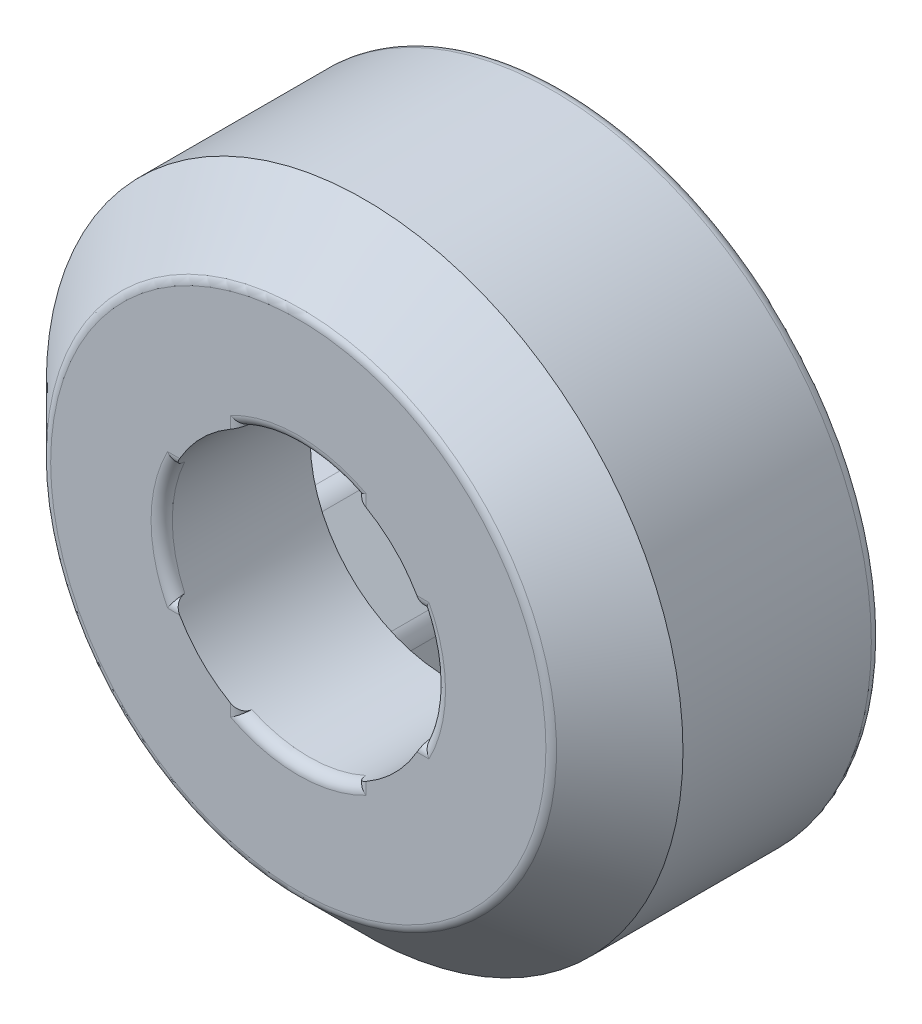
SolidWorks part; units mm, degrees
ref_plane "Front Plane" through (0, 0, 0) normal (0, 0, 1) x (1, 0, 0)
ref_plane "Top Plane" through (0, 0, 0) normal (0, 1, 0) x (1, 0, 0)
ref_plane "Right Plane" through (0, 0, 0) normal (1, 0, 0) x (0, 0, -1)
sketch "Sketch2" plane through (0, 0, 0) normal (0, 0, 1) x (1, 0, 0)
  line L0 (1.0775, 1.0775) -> (2.3387, 1.0775)
  line L1 (-2.3387, 1.0775) -> (-1.0775, 1.0775)
  line L2 (-1.0775, -1.0775) -> (-1.0775, -2.3387)
  line L3 (-2.3387, -1.0775) -> (-1.0775, -1.0775)
  line L4 (1.0775, -1.0775) -> (2.3387, -1.0775)
  line L5 (1.0775, -1.0775) -> (1.0775, -2.3387)
  line L6 (0, -2.575) -> (0, 2.575) construction
  line L8 (-1.0775, 2.3387) -> (-1.0775, 1.0775)
  line L10 (1.0775, 2.3387) -> (1.0775, 1.0775)
  circle A0 centre (0, 0) radius 4.95 construction
  arc A1 (-1.0775, -2.3387) -> (1.0775, -2.3387) centre (0, 0) ccw
  arc A2 (2.3387, -1.0775) -> (2.3387, 1.0775) centre (0, 0) ccw
  arc A3 (1.0775, 2.3387) -> (-1.0775, 2.3387) centre (0, 0) ccw
  arc A4 (-2.3387, 1.0775) -> (-2.3387, -1.0775) centre (0, 0) ccw
  point P7 (0, 0)
  point P12 (0, 0)
  dimension "D1" = 5.15
  dimension "D2" = 9.9
  dimension "D3" = 2.155
sketch "Sketch3" plane through (0, 0, 0) normal (1, 0, 0) x (0, 0, -1)
  line L0 (-1.5, 0) -> (3.5, 0)
  line L1 (-1.5, 0) -> (-1.5, 3.75)
  line L2 (3.5, 6) -> (5.2896, 6) construction
  line L3 (1.5, 0) -> (1.5, 1.7082) construction
  line L4 (1, 0) -> (1, 6) construction
  line L5 (3.5, 0) -> (3.5, 6)
  line L6 (-1.5, 3.75) -> (-4.0782, 3.75) construction
  line L7 (3.5, 6) -> (1, 6)
  line L8 (1, 6) -> (-1.5, 6)
  line L9 (-1.5, 6) -> (-1.5, 3.75)
  dimension "D1" = 1.5
  dimension "D2" = 3.75
  dimension "D3" = 3
  dimension "D4" = 2
  dimension "D5" = 6
  dimension "D6" = 2.5
revolve "Revolve1" add sketch "Sketch3" angle 360 about L0
extrude "Cut-Extrude1" cut sketch "Sketch2" against normal through all both and the other way through all
sketch "Sketch4" plane through (0, 0, -3.5) normal (0, 0, -1) x (-1, 0, 0)
  line L0 (0, 5) -> (0, 0) construction
  line L1 (0, 0) -> (-5, 0) construction
  line L2 (-1.5, 4.7697) -> (-1.5, 3.0962)
  line L3 (-1.5, 3.0962) -> (-3.0962, 1.5)
  line L4 (-3.0962, 1.5) -> (-4.7697, 1.5)
  line L5 (-1.5, 4.7697) -> (0, 4.7697) construction
  line L6 (-4.7697, 0) -> (-4.7697, 1.5) construction
  line L7 (1.5, 3.0962) -> (1.5, 4.7697)
  line L8 (3.0962, 1.5) -> (1.5, 3.0962)
  line L9 (4.7697, 1.5) -> (3.0962, 1.5)
  line L10 (3.0962, -1.5) -> (4.7697, -1.5)
  line L11 (1.5, -3.0962) -> (3.0962, -1.5)
  line L12 (1.5, -4.7697) -> (1.5, -3.0962)
  line L13 (-1.5, -3.0962) -> (-1.5, -4.7697)
  line L14 (-3.0962, -1.5) -> (-1.5, -3.0962)
  line L15 (-4.7697, -1.5) -> (-3.0962, -1.5)
  arc A0 (0, 5) -> (-1.5, 4.7697) centre (0, 0) ccw
  arc A1 (-4.7697, 1.5) -> (-5, 0) centre (0, 0) ccw
  arc A2 (1.5, 4.7697) -> (0, 5) centre (0, 0) ccw
  arc A3 (5, 0) -> (4.7697, 1.5) centre (0, 0) ccw
  arc A4 (4.7697, -1.5) -> (5, 0) centre (0, 0) ccw
  arc A5 (0, -5) -> (1.5, -4.7697) centre (0, 0) ccw
  arc A6 (-1.5, -4.7697) -> (0, -5) centre (0, 0) ccw
  arc A7 (-5, 0) -> (-4.7697, -1.5) centre (0, 0) ccw
  point P31 (0, 0)
  dimension "D1" = 5
  dimension "D2" = 3.25
  dimension "D3" = 1.5
  dimension "D4" = 45
  dimension "D5" = 4
extrude "Cut-Extrude2" cut sketch "Sketch4" against normal blind 2.2
fillet "Fillet1" radius 0.5 8 edges at (3.0962, -1.5, -2.4) (1.5, -3.0962, -2.4) (-1.5, -3.0962, -2.4) (-3.0962, -1.5, -2.4) (-3.0962, 1.5, -2.4) (-1.5, 3.0962, -2.4) (1.5, 3.0962, -2.4) (3.0962, 1.5, -2.4)
chamfer "Chamfer1" distance 1.25 angle 45 1 edges at (6, 0, 1.5)
fillet "Fillet2" radius 0.2 38 edges at (-1.0775, -1.7081, 1.5) (0, -2.575, 1.5) (1.0775, -1.7081, 1.5) (1.7081, -1.0775, 1.5) (2.575, 0, 1.5) (1.7081, 1.0775, 1.5) (1.0775, 1.7081, 1.5) (0, 2.575, 1.5) (-1.0775, 1.7081, 1.5) (-1.7081, 1.0775, 1.5) (-2.575, 0, 1.5) (-1.7081, -1.0775, 1.5) (6, 0, -3.5) (1.5381, -3.112, -3.5) (1.5, -4.0365, -3.5) (0, -5, -3.5) (-1.5, -4.0365, -3.5) (-1.5381, -3.112, -3.5) (-2.2981, -2.2981, -3.5) (-3.112, -1.5381, -3.5) (-4.0365, -1.5, -3.5) (-5, 0, -3.5) (-4.0365, 1.5, -3.5) (-3.112, 1.5381, -3.5) (-2.2981, 2.2981, -3.5) (-1.5381, 3.112, -3.5) (-1.5, 4.0365, -3.5) (0, 5, -3.5) (1.5, 4.0365, -3.5) (1.5381, 3.112, -3.5) (2.2981, 2.2981, -3.5) (3.112, 1.5381, -3.5) (4.0365, 1.5, -3.5) (5, 0, -3.5) (4.0365, -1.5, -3.5) (3.112, -1.5381, -3.5) (2.2981, -2.2981, -3.5) (-4.75, 0, 1.5)
sketch "Sketch5" plane through (0, 0, -1.3) normal (0, 0, -1) x (-1, 0, 0)
  circle A0 centre (0, 0) radius 2.575
  dimension "D1" = 5.15
extrude "Cut-Extrude3" cut sketch "Sketch5" against normal through all both and the other way through all
